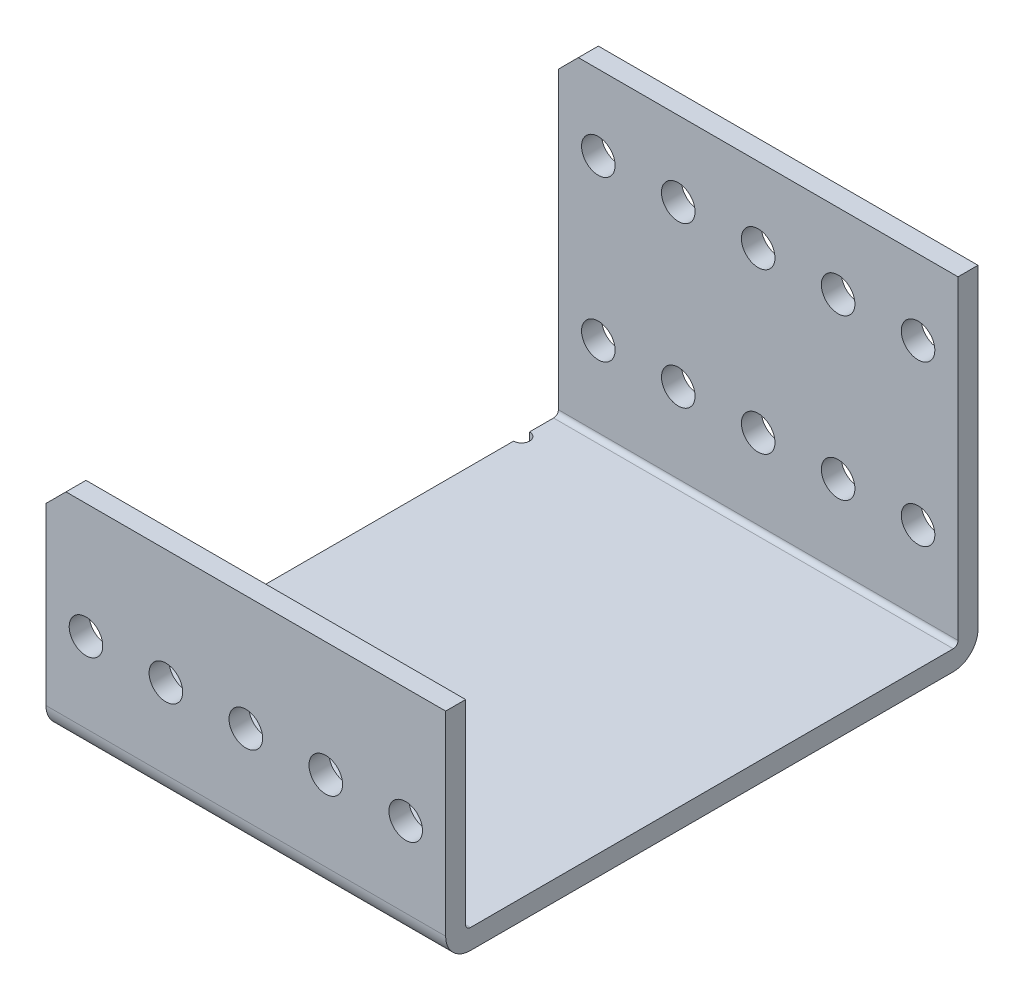
SolidWorks part; units mm, degrees
ref_plane "Front Plane" through (0, 0, 0) normal (0, 0, 1) x (1, 0, 0)
ref_plane "Top Plane" through (0, 0, 0) normal (0, 1, 0) x (1, 0, 0)
ref_plane "Right Plane" through (0, 0, 0) normal (1, 0, 0) x (0, 0, -1)
ref_plane "Plane4" through (0, 57.8164, 0) normal (0, 1, 0) x (1, 0, 0)
sketch "Sketch1" plane through (0, 57.8164, 0) normal (0, 1, 0) x (1, 0, 0)
  line L0 (602.398, -145.5605) -> (602.398, -60.9785)
  line L1 (602.398, -60.9785) -> (-96.102, -60.9785)
  line L2 (-96.102, -60.9785) -> (-96.102, -145.5605)
  line L3 (-96.102, -145.5605) -> (602.398, -145.5605)
  dimension "D1" = 698.5
extrude "Boss-Extrude1" add sketch "Sketch1" against normal blind 34.925
sketch "Sketch2" plane through (602.398, 0, 0) normal (1, 0, 0) x (0, 0, -1)
  line L0 (-60.9785, 57.8164) -> (-142.3855, 57.8164)
  line L1 (-142.3855, 57.8164) -> (-142.3855, 26.0664)
  line L2 (-142.3855, 26.0664) -> (-60.9785, 26.0664)
  line L3 (-60.9785, 26.0664) -> (-60.9785, 57.8164)
extrude "Cut-Extrude1" cut sketch "Sketch2" against normal through all
sketch "Sketch3" plane through (0, 26.0664, 0) normal (0, 1, 0) x (-1, 0, 0)
  line L0 (96.102, 60.9785) -> (-602.398, 60.9785)
  line L1 (-602.398, 60.9785) -> (-602.398, 64.1535)
  line L2 (-602.398, 64.1535) -> (96.102, 64.1535)
  line L3 (96.102, 64.1535) -> (96.102, 60.9785)
  line L5 (-602.398, 142.3855) -> (-602.398, 60.9785) construction
  line L6 (96.102, 142.3855) -> (96.102, 60.9785) construction
extrude "Boss-Extrude2" add sketch "Sketch3" along normal blind 50.8
hole_wizard "M2 Clearance Hole1" positions "Sketch5" profile "Sketch4" hole size "M2" standard "ANSI Metric" end condition through all
sketch "Sketch5" plane through (0, 26.0664, 0) normal (0, 1, 0) x (1, 0, 0)
  point P0 (-96.102, -136.5435)
  point P1 (-96.102, -69.9955)
sketch "Sketch4" plane through (-96.102, 26.0664, 136.5435) normal (1, 0, 0) x (0, 0, 1)
  line L0 (0, 0) -> (0, 3.175)
  line L1 (0, 3.175) -> (1.27, 3.175)
  line L2 (1.27, 3.175) -> (1.27, 0)
  line L5 (1.27, 0) -> (0, 0)
  line L11 (0, -6.35) -> (0, 107.95) construction
  dimension "Thru Hole Dia." = 2.54
  dimension "Thru Hole Depth" = 3.175
hole_wizard "M5 Clearance Hole1" positions "Sketch7" profile "Sketch6" hole size "M5" standard "ANSI Metric" end condition through all
sketch "Sketch7" plane through (0, 0, 60.9785) normal (0, 0, -1) x (-1, 0, 0)
  point P0 (-469.048, 64.9284)
  point P1 (-481.748, 64.9284)
  point P2 (-469.048, 39.5284)
  point P3 (-481.748, 39.5284)
  point P4 (-456.348, 39.5284)
  point P5 (-443.648, 39.5284)
  point P6 (-430.948, 39.5284)
  point P7 (-418.248, 39.5284)
  point P8 (-405.548, 39.5284)
  point P9 (-392.848, 39.5284)
  point P10 (-380.148, 39.5284)
  point P11 (-367.448, 39.5284)
  point P12 (-354.748, 39.5284)
  point P13 (-342.048, 39.5284)
  point P14 (-329.348, 39.5284)
  point P15 (-316.648, 39.5284)
  point P16 (-303.948, 39.5284)
  point P17 (-291.248, 39.5284)
  point P18 (-278.548, 39.5284)
  point P19 (-265.848, 39.5284)
  point P20 (-253.148, 39.5284)
  point P21 (-240.448, 39.5284)
  point P22 (-227.748, 39.5284)
  point P23 (-215.048, 39.5284)
  point P24 (-202.348, 39.5284)
  point P25 (-189.648, 39.5284)
  point P26 (-176.948, 39.5284)
  point P27 (-164.248, 39.5284)
  point P28 (-151.548, 39.5284)
  point P29 (-138.848, 39.5284)
  point P30 (-126.148, 39.5284)
  point P31 (-113.448, 39.5284)
  point P32 (-100.748, 39.5284)
  point P33 (-88.048, 39.5284)
  point P34 (-75.348, 39.5284)
  point P35 (-62.648, 39.5284)
  point P36 (-49.948, 39.5284)
  point P37 (-37.248, 39.5284)
  point P38 (-24.548, 39.5284)
  point P39 (-11.848, 39.5284)
  point P40 (0.852, 39.5284)
  point P41 (13.552, 39.5284)
  point P42 (26.252, 39.5284)
  point P43 (38.952, 39.5284)
  point P44 (51.652, 39.5284)
  point P45 (64.352, 39.5284)
  point P46 (77.052, 39.5284)
  point P47 (89.752, 39.5284)
  point P48 (-456.348, 64.9284)
  point P49 (-443.648, 64.9284)
  point P50 (-430.948, 64.9284)
  point P51 (-418.248, 64.9284)
  point P52 (-405.548, 64.9284)
  point P53 (-392.848, 64.9284)
  point P54 (-380.148, 64.9284)
  point P55 (-367.448, 64.9284)
  point P56 (-354.748, 64.9284)
  point P57 (-342.048, 64.9284)
  point P58 (-329.348, 64.9284)
  point P59 (-316.648, 64.9284)
  point P60 (-303.948, 64.9284)
  point P61 (-291.248, 64.9284)
  point P62 (-278.548, 64.9284)
  point P63 (-265.848, 64.9284)
  point P64 (-253.148, 64.9284)
  point P65 (-240.448, 64.9284)
  point P66 (-227.748, 64.9284)
  point P67 (-215.048, 64.9284)
  point P68 (-202.348, 64.9284)
  point P69 (-189.648, 64.9284)
  point P70 (-176.948, 64.9284)
  point P71 (-164.248, 64.9284)
  point P72 (-151.548, 64.9284)
  point P73 (-138.848, 64.9284)
  point P74 (-126.148, 64.9284)
  point P75 (-113.448, 64.9284)
  point P76 (-100.748, 64.9284)
  point P77 (-88.048, 64.9284)
  point P78 (-75.348, 64.9284)
  point P79 (-62.648, 64.9284)
  point P80 (-49.948, 64.9284)
  point P81 (-37.248, 64.9284)
  point P82 (-24.548, 64.9284)
  point P83 (-11.848, 64.9284)
  point P84 (0.852, 64.9284)
  point P85 (13.552, 64.9284)
  point P86 (26.252, 64.9284)
  point P87 (38.952, 64.9284)
  point P88 (51.652, 64.9284)
  point P89 (64.352, 64.9284)
  point P90 (77.052, 64.9284)
  point P91 (89.752, 64.9284)
  point P97 (-494.448, 64.9284)
  point P98 (-494.448, 39.5284)
  point P99 (-507.148, 64.9284)
  point P100 (-507.148, 39.5284)
  point P101 (-519.848, 64.9284)
  point P102 (-519.848, 39.5284)
  point P103 (-532.548, 64.9284)
  point P104 (-532.548, 39.5284)
  point P105 (-545.248, 64.9284)
  point P106 (-545.248, 39.5284)
  point P107 (-557.948, 64.9284)
  point P108 (-557.948, 39.5284)
  point P109 (-570.648, 64.9284)
  point P110 (-570.648, 39.5284)
  point P111 (-583.348, 64.9284)
  point P112 (-583.348, 39.5284)
  point P113 (-596.048, 64.9284)
  point P114 (-596.048, 39.5284)
  dimension "D1" = 10
sketch "Sketch6" plane through (469.048, 64.9284, 60.9785) normal (1, 0, 0) x (0, 1, 0)
  line L0 (0, 0) -> (0, 84.582)
  line L1 (0, 84.582) -> (2.667, 84.582)
  line L2 (2.667, 84.582) -> (2.667, 0)
  line L5 (2.667, 0) -> (0, 0)
  line L11 (0, -6.35) -> (0, 107.95) construction
  dimension "Thru Hole Dia." = 5.334
  dimension "Thru Hole Depth" = 84.582
chamfer "Chamfer1" distance 3.175 angle 45 4 edges at (602.398, 76.8664, 62.566) (-96.102, 57.8164, 143.973) (602.398, 57.8164, 143.973) (-96.102, 76.8664, 62.566)
fillet "Fillet1" radius 0.762 2 edges at (253.148, 26.0664, 64.1535) (253.148, 26.0664, 142.3855) tangent propagation no
fillet "Fillet2" radius 3.937 2 edges at (253.148, 22.8914, 145.5605) (253.148, 22.8914, 60.9785) tangent propagation no
sketch "Sketch8" plane through (0, 0, 60.9785) normal (0, 0, -1) x (-1, 0, 0)
  line L1 (-693.323, 170.3588) -> (32.602, 170.3588)
  line L2 (-693.323, 170.3588) -> (-693.323, -47.8575)
  line L3 (-693.323, -47.8575) -> (32.602, -47.8575)
  line L4 (32.602, 170.3588) -> (32.602, -47.8575)
  line L5 (-693.323, 170.3588) -> (32.602, -47.8575) construction
  line L6 (-693.323, -47.8575) -> (32.602, 170.3588) construction
  line L7 (38.952, 39.5284) -> (26.252, 39.5284) construction
  point P4 (-330.3605, 61.2506)
  point P5 (32.602, 39.5284)
extrude "Cut-Extrude2" cut sketch "Sketch8" against normal through all
sketch "Sketch9" plane through (0, 22.8914, 0) normal (0, -1, 0) x (1, 0, 0)
  circle A2 centre (-54.827, 127.204) radius 1.5875
  circle A3 centre (-73.877, 127.204) radius 1.5875
extrude "Cut-Extrude3" cut sketch "Sketch9" against normal up to next
